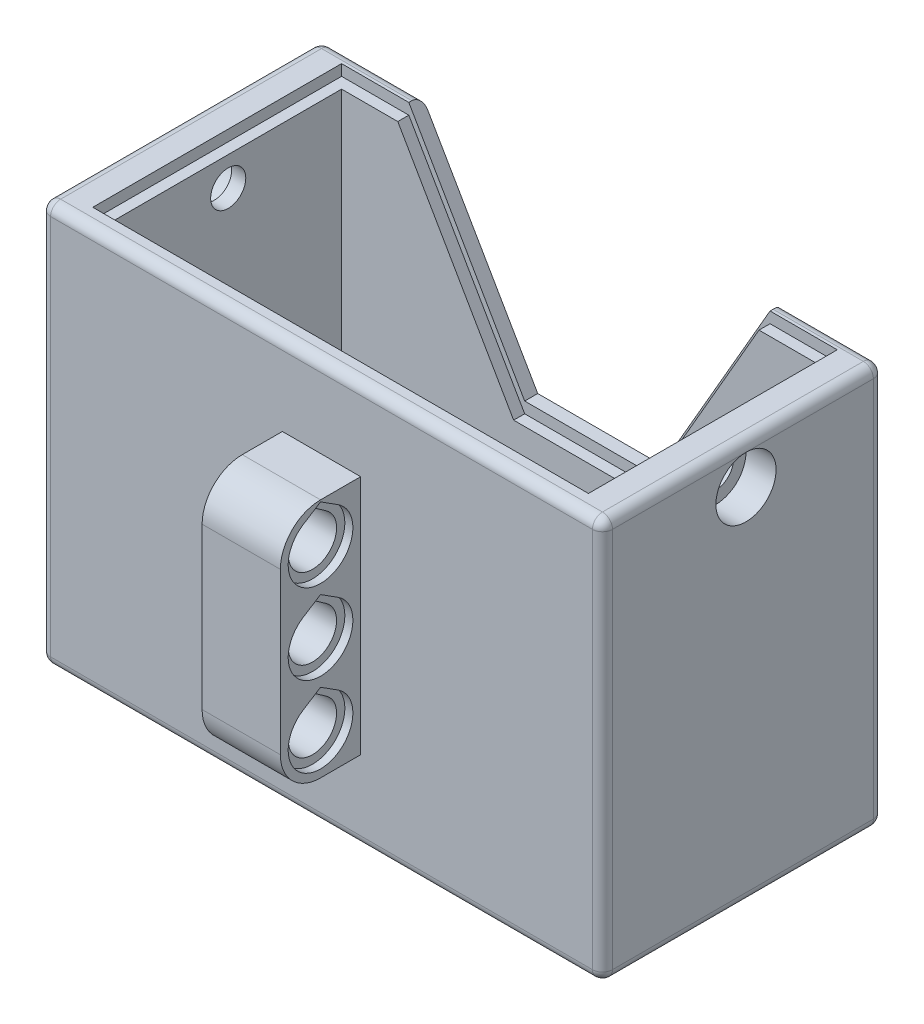
SolidWorks part; units mm, degrees
ref_plane "Ebene vorne" through (0, 0, 0) normal (0, 0, 1) x (1, 0, 0)
ref_plane "Ebene oben" through (0, 0, 0) normal (0, 1, 0) x (1, 0, 0)
ref_plane "Ebene rechts" through (0, 0, 0) normal (1, 0, 0) x (0, 0, -1)
sketch "Skizze1" plane through (0, 0, 0) normal (0, 1, 0) x (1, 0, 0)
  line L0 (0, 0) -> (0, 36.8308) construction
  line L1 (-28, 28) -> (-28, 0)
  line L2 (-28, 28) -> (28, 28)
  line L3 (-28, 0) -> (28, 0)
  line L4 (28, 28) -> (28, 0)
  line L5 (-28, 28) -> (28, 0) construction
  line L6 (-28, 0) -> (28, 28) construction
  line L7 (-28, 14) -> (28, 14) construction
  circle A0 centre (-13.05, 14) radius 8.5
  circle A1 centre (13.05, 14) radius 8.5
  point P3 (0, 0)
  point P4 (0, 14)
  dimension "D3" = 17
  dimension "D4" = 13.05
  dimension "D1" = 56
  dimension "D2" = 28
extrude "Front" add sketch "Skizze1" along normal blind 12
sketch "Skizze2" plane through (0, 12, 0) normal (0, 1, 0) x (1, 0, 0)
  line L1 (-28, 28) -> (28, 28)
  line L2 (-28, 28) -> (-28, 0)
  line L3 (-28, 0) -> (28, 0)
  line L4 (28, 28) -> (28, 0)
  line L5 (-23.6, 25.6) -> (23.6, 25.6)
  line L6 (-23.6, 25.6) -> (-23.6, 3)
  line L7 (-23.6, 3) -> (23.6, 3)
  line L8 (23.6, 25.6) -> (23.6, 3)
  dimension "D1" = 4.4
  dimension "D2" = 4.4
  dimension "D3" = 2.4
  dimension "D4" = 3
extrude "Walls" add sketch "Skizze2" along normal blind 28
sketch "Skizze3" plane through (0, 0, -28) normal (0, 0, -1) x (-1, 0, 0)
  line L0 (0, 40) -> (0, 0) construction
  line L1 (-28, 40) -> (28, 40) construction
  line L2 (-28, 0) -> (28, 0) construction
  line L3 (-18, 40) -> (-6.453, 20)
  line L4 (-6.453, 20) -> (6.453, 20)
  line L5 (-28, 40) -> (-28, 0) construction
  line L6 (-18, 40) -> (18, 40)
  line L7 (18, 40) -> (6.453, 20)
  point P13 (0, 20)
  dimension "D1" = 10
  dimension "D2" = 20
  dimension "D3" = 120
extrude "Ausschnittfür Montage" cut sketch "Skizze3" against normal up to surface (2.4 mm away) up to face at (0, 26, -25.6)
sketch "Skizze4" plane through (0, 40, 0) normal (0, 1, 0) x (1, 0, 0)
  line L0 (-18, 25.6) -> (-23.6, 25.6)
  line L1 (-23.6, 25.6) -> (-23.6, 3)
  line L2 (-23.6, 3) -> (23.6, 3)
  line L3 (23.6, 3) -> (23.6, 25.6)
  line L4 (23.6, 25.6) -> (18, 25.6)
  line L5 (-18, 26.7) -> (-24.7, 26.7)
  line L6 (-24.7, 26.7) -> (-24.7, 1.9)
  line L7 (-24.7, 1.9) -> (24.7, 1.9)
  line L8 (24.7, 1.9) -> (24.7, 26.7)
  line L9 (24.7, 26.7) -> (18, 26.7)
  line L10 (-18, 26.7) -> (-18, 25.6)
  line L11 (18, 26.7) -> (18, 25.6)
  dimension "D1" = 1.1
extrude "Schnitt-Linear austragen2" cut sketch "Skizze4" against normal blind 1.1
sketch "Skizze5" plane through (0, 0, -25.6) normal (0, 0, 1) x (1, 0, 0)
  line L0 (-18, 38.9) -> (-18, 40)
  line L1 (-18, 40) -> (-6.453, 20)
  line L2 (-6.453, 20) -> (6.453, 20)
  line L3 (6.453, 20) -> (18, 40)
  line L4 (18, 40) -> (18, 38.9)
  line L5 (18, 38.9) -> (6.453, 18.9)
  line L6 (6.453, 18.9) -> (-6.453, 18.9)
  line L7 (-6.453, 18.9) -> (-18, 38.9)
  dimension "D1" = 1.1
extrude "Schnitt-Linear austragen3" cut sketch "Skizze5" against normal blind 1.1
sketch "Skizze6" plane through (0, 12, 0) normal (0, 1, 0) x (1, 0, 0)
  line L0 (0, 0) -> (0, 28) construction
  line L1 (-28, 0) -> (28, 0) construction
  line L2 (6.453, 28) -> (-6.453, 28) construction
  line L3 (-21.2, 22.6) -> (-21.2, 5) construction
  line L4 (-23.6, 3) -> (-23.6, 25.6) construction
  line L5 (-23.6, 25.6) -> (-18, 25.6) construction
  line L6 (23.6, 3) -> (-23.6, 3) construction
  line L7 (5, 18.6) -> (-5, 18.6)
  line L8 (-5, 18.6) -> (-9.9015, 25.6)
  line L9 (23.6, 25.6) -> (-23.6, 25.6) construction
  line L10 (-9.9015, 25.6) -> (9.9015, 25.6)
  line L11 (21.2, 22.6) -> (21.2, 5) construction
  line L12 (5, 18.6) -> (9.9015, 25.6)
  line L18 (5, 7) -> (5, 3)
  line L19 (5, 7) -> (-5, 7)
  line L20 (5, 3) -> (-5, 3)
  line L21 (-5, 7) -> (-5, 3)
  line L22 (5, 7) -> (-5, 3) construction
  line L23 (5, 3) -> (-5, 7) construction
  line L24 (-23.6, 3) -> (23.6, 3) construction
  circle A0 centre (-21.2, 22.6) radius 0.75
  circle A1 centre (-21.2, 5) radius 0.75
  circle A2 centre (21.2, 5) radius 0.75
  circle A3 centre (21.2, 22.6) radius 0.75
  point P27 (0, 25.6)
  point P28 (0, 18.6)
  point P29 (0, 5)
  dimension "D2" = 3
  dimension "D3" = 2
  dimension "D4" = 1.5
  dimension "D5" = 1.5
  dimension "D1" = 2.4
  dimension "D6" = 7
  dimension "D7" = 125
  dimension "D8" = 5
  dimension "D9" = 10
  dimension "D10" = 4
  dimension "D11" = 5
  dimension "D12" = 0
extrude "Ausschnitt_Montage_Sensor" cut sketch "Skizze6" against normal blind 6
sketch "Skizze7" plane through (0, 0, -3) normal (0, 0, -1) x (-1, 0, 0)
  line L0 (0, 0) -> (0, 40) construction
  line L1 (24.7, 40) -> (-24.7, 40) construction
  circle A0 centre (-6, 30.4) radius 1.75
  circle A1 centre (6, 30.4) radius 1.75
  dimension "D1" = 9.6
  dimension "D2" = 6
  dimension "D3" = 3.5
extrude "Aufsatz-Linear austragen3" add sketch "Skizze7" along normal blind 1
sketch "Skizze8" plane through (0, 0, -4) normal (0, 0, -1) x (-1, 0, 0)
  circle A0 centre (-6, 30.4) radius 0.9
  circle A1 centre (6, 30.4) radius 0.9
  dimension "D1" = 1.8
  dimension "D2" = 1.8
extrude "Schnitt-Linear austragen5" cut sketch "Skizze8" against normal offset from surface (3 mm away) 1 up to face at (0, 20, 0)
sketch "Skizze9" plane through (28, 0, 0) normal (1, 0, 0) x (0, 0, -1)
  line L0 (28, 40) -> (28, 0) construction
  line L1 (0, 40) -> (28, 40) construction
  circle A0 centre (14.3, 36) radius 1.75
  dimension "D1" = 3.5
  dimension "D2" = 13.7
  dimension "D3" = 4
extrude "Schnitt-Linear austragen6" cut sketch "Skizze9" against normal up to surface (4.4 mm away) up to face at (23.6, 25.45, -14.3)
sketch "Skizze10" plane through (28, 0, 0) normal (1, 0, 0) x (0, 0, -1)
  circle A0 centre (14.3, 36) radius 3
  dimension "D1" = 6
extrude "Schnitt-Linear austragen7" cut sketch "Skizze10" against normal blind 3
mirror "Spiegeln1" about plane through (0, 0, 0) normal (1, 0, 0) of "Schnitt-Linear austragen6", "Schnitt-Linear austragen7"
fillet "Verrundung1" radius 1 13 edges at (0, 0, 0) (0, 0, -28) (28, 0, -14) (28, 20, 0) (28, 20, -28) (23, 40, -28) (28, 40, -14) (-28, 0, -14) (0, 40, 0) (-28, 20, 0) (-23, 40, -28) (-28, 40, -14) (-28, 20, -28)
fillet "Verrundung2" radius 2 2 edges at (13.05, 0, -22.5) (-13.05, 0, -5.5)
sketch "Skizze11" plane through (0, 0, 0) normal (1, 0, 0) x (0, 0, -1)
  line L0 (0, 32) -> (-4, 32)
  line L1 (0, 1) -> (0, 39) construction
  line L2 (-8, 28) -> (-8, 12)
  line L3 (-4, 8) -> (0, 8)
  line L4 (0, 8) -> (0, 32)
  line L5 (27, 0) -> (1, 0) construction
  line L6 (-4, 12) -> (-4, 24.0167) construction
  line L7 (-4, 14.9299) -> (-5.3766, 13.966)
  line L8 (-4, 14.9299) -> (-2.6234, 13.966)
  line L9 (-4, 22.9299) -> (-5.3766, 21.966)
  line L10 (-4, 22.9299) -> (-2.6234, 21.966)
  line L11 (-4, 30.9299) -> (-5.3766, 29.966)
  line L12 (-4, 30.9299) -> (-2.6234, 29.966)
  arc A0 (-5.3766, 13.966) -> (-2.6234, 13.966) centre (-4, 12) ccw
  arc A1 (-5.3766, 21.966) -> (-2.6234, 21.966) centre (-4, 20) ccw
  arc A2 (-5.3766, 29.966) -> (-2.6234, 29.966) centre (-4, 28) ccw
  arc A3 (-8, 12) -> (-4, 8) centre (-4, 12) ccw
  arc A4 (-4, 32) -> (-8, 28) centre (-4, 28) ccw
  point P23 (-8, 8)
  point P26 (-8, 32)
  dimension "D4" = 4.8
  dimension "D6" = 12
  dimension "D9" = 4
  dimension "D1" = 4
  dimension "D2" = 4
  dimension "D3" = 8
  dimension "D5" = 24
  dimension "D7" = 110
  dimension "D8" = 3
extrude "Aufsatz-Linear austragen4" add sketch "Skizze11" along normal blind 3.9
sketch "Skizze12" plane through (3.9, 0, 0) normal (1, 0, 0) x (0, 0, -1)
  line L0 (-4, 28) -> (-4, 39.3802) construction
  line L1 (-4, 31.8238) -> (-5.7328, 30.7199)
  line L2 (-4, 31.8238) -> (-2.2672, 30.7199)
  line L3 (-4, 23.8238) -> (-5.7328, 22.7199)
  line L4 (-4, 23.8238) -> (-2.2672, 22.7199)
  line L5 (-4, 15.8238) -> (-5.7328, 14.7199)
  line L6 (-4, 15.8238) -> (-2.2672, 14.7199)
  arc A0 (-5.7328, 30.7199) -> (-2.2672, 30.7199) centre (-4, 28) ccw
  arc A1 (-5.7328, 22.7199) -> (-2.2672, 22.7199) centre (-4, 20) ccw
  arc A2 (-5.7328, 14.7199) -> (-2.2672, 14.7199) centre (-4, 12) ccw
  dimension "D1" = 6.45
  dimension "D2" = 115
  dimension "D3" = 3
extrude "Schnitt-Linear austragen8" cut sketch "Skizze12" against normal blind 0.8
mirror "Spiegeln2" about plane through (0, 0, 0) normal (1, 0, 0) of "Aufsatz-Linear austragen4", "Schnitt-Linear austragen8"
